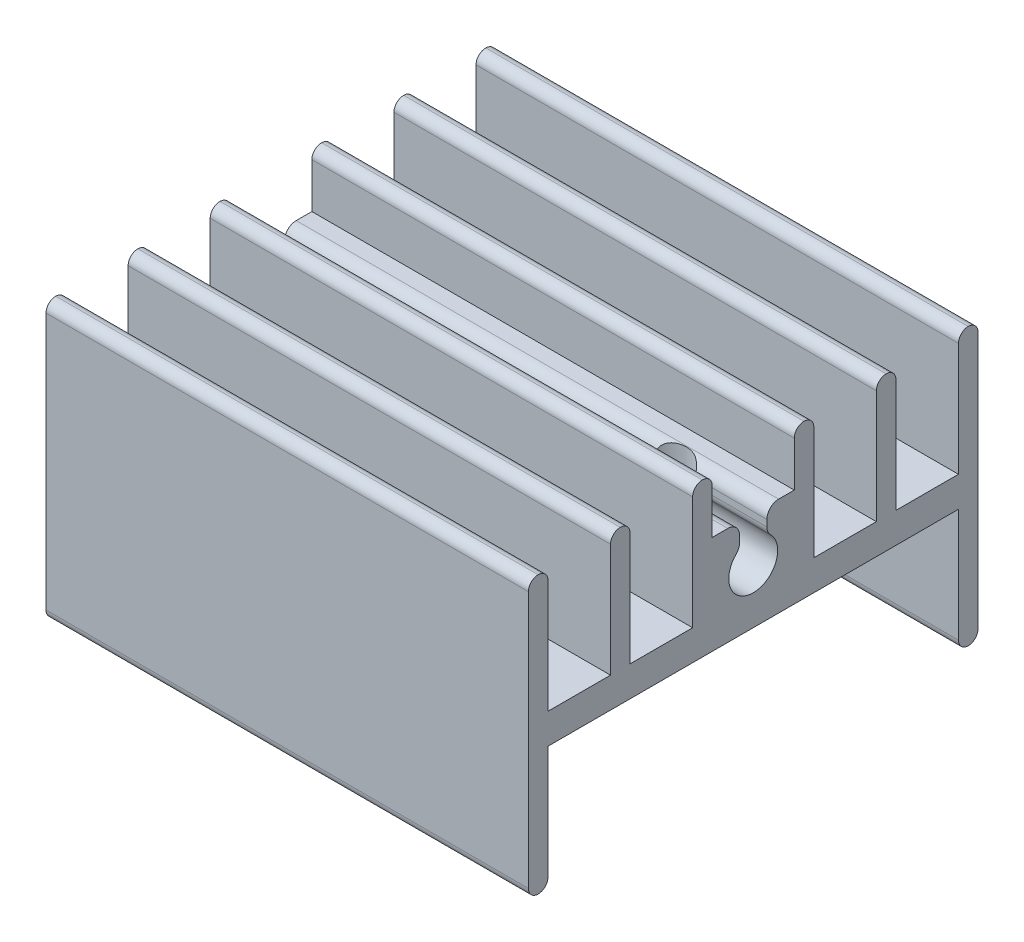
SolidWorks part; units mm, degrees
ref_plane "Front Plane" through (0, 0, 0) normal (0, 0, 1) x (1, 0, 0)
ref_plane "Top Plane" through (0, 0, 0) normal (0, 1, 0) x (1, 0, 0)
ref_plane "Right Plane" through (0, 0, 0) normal (1, 0, 0) x (0, 0, -1)
sketch "Sketch1" plane through (0, 0, 0) normal (0, 1, 0) x (1, 0, 0)
  line L1 (-12.34, 11.5) -> (12.34, 11.5)
  line L2 (-12.34, 11.5) -> (-12.34, -11.5)
  line L3 (-12.34, -11.5) -> (12.34, -11.5)
  line L4 (12.34, 11.5) -> (12.34, -11.5)
  line L5 (-12.34, 11.5) -> (12.34, -11.5) construction
  line L6 (-12.34, -11.5) -> (12.34, 11.5) construction
  point P0 (0, 0)
  dimension "D1" = 24.68
  dimension "D2" = 23
extrude "Boss-Extrude1" add sketch "Sketch1" along normal blind 1.55
sketch "Sketch2" plane through (0, 1.55, 0) normal (0, 1, 0) x (1, 0, 0)
  line L0 (12.34, -11.5) -> (12.34, 11.5) construction
  line L1 (-12.34, 11.5) -> (12.34, 11.5)
  line L2 (-12.34, 11.5) -> (-12.34, 10.5)
  line L3 (-12.34, 10.5) -> (12.34, 10.5)
  line L4 (12.34, 11.5) -> (12.34, 10.5)
  line L6 (-12.34, -11.5) -> (12.34, -11.5)
  line L7 (-12.34, -11.5) -> (-12.34, -10.5)
  line L8 (-12.34, -10.5) -> (12.34, -10.5)
  line L9 (12.34, -11.5) -> (12.34, -10.5)
  dimension "D1" = 1
  dimension "D2" = 1
extrude "Boss-Extrude2" add sketch "Sketch2" along normal blind 6.3 and the other way blind 7.85
sketch "Sketch3" plane through (0, 1.55, 0) normal (0, 1, 0) x (1, 0, 0)
  line L0 (-12.34, 10.5) -> (-12.34, -10.5) construction
  line L1 (-12.34, 7.3) -> (12.34, 7.3)
  line L2 (-12.34, 7.3) -> (-12.34, 6.3)
  line L3 (-12.34, 6.3) -> (12.34, 6.3)
  line L4 (12.34, 7.3) -> (12.34, 6.3)
  line L5 (12.34, -10.5) -> (12.34, 10.5) construction
  line L6 (-12.34, 10.5) -> (12.34, 10.5) construction
  line L8 (-12.34, -6.3) -> (12.34, -6.3)
  line L9 (-12.34, -6.3) -> (-12.34, -7.3)
  line L10 (-12.34, -7.3) -> (12.34, -7.3)
  line L11 (12.34, -6.3) -> (12.34, -7.3)
  dimension "D1" = 3.2
  dimension "D2" = 1
  dimension "D3" = 3.2
  dimension "D4" = 1
extrude "Boss-Extrude3" add sketch "Sketch3" along normal blind 6.3
sketch "Sketch4" plane through (0, 1.55, 0) normal (0, 1, 0) x (1, 0, 0)
  line L0 (-12.34, 6.3) -> (-12.34, -6.3) construction
  line L1 (-12.34, 3.1) -> (12.34, 3.1)
  line L2 (-12.34, 3.1) -> (-12.34, -3.1)
  line L3 (-12.34, -3.1) -> (12.34, -3.1)
  line L4 (12.34, 3.1) -> (12.34, -3.1)
  line L5 (12.34, -6.3) -> (12.34, 6.3) construction
  line L6 (-12.34, 6.3) -> (12.34, 6.3) construction
  line L7 (12.34, -6.3) -> (-12.34, -6.3) construction
  dimension "D1" = 3.2
  dimension "D2" = 3.2
extrude "Boss-Extrude4" add sketch "Sketch4" along normal blind 6.3
sketch "Sketch5" plane through (12.34, 0, 0) normal (1, 0, 0) x (0, 0, -1)
  line L0 (-3.1, 1.55) -> (3.1, 1.55) construction
  line L1 (0, 1.55) -> (0, 7.85) construction
  line L2 (-3.1, 7.85) -> (3.1, 7.85) construction
  line L3 (-2.1, 5.05) -> (-0.7, 5.05)
  line L4 (-3.1, 4.05) -> (-2.1, 4.05) construction
  line L5 (3.1, 7.85) -> (3.1, 1.55) construction
  line L6 (-3.1, 7.85) -> (-3.1, 1.55) construction
  line L7 (-0.7, 5.05) -> (-0.7, 3.8356)
  line L8 (0.7, 5.05) -> (0.7, 3.8356)
  line L9 (0.7, 5.05) -> (2.1, 5.05)
  line L10 (-2.1, 8.15) -> (-2.1, 5.05)
  line L11 (2.1, 8.15) -> (2.1, 5.05)
  line L12 (-2.1, 8.15) -> (2.1, 8.15)
  line L13 (-0.7, 4.05) -> (3.1, 4.05) construction
  arc A0 (-0.7, 3.8356) -> (0.7, 3.8356) centre (0, 2.8) ccw
  point P11 (0, 4.7)
  dimension "D1" = 2.5
  dimension "D2" = 1
  dimension "D3" = 0.7
  dimension "D4" = 1.4
  dimension "D5" = 1
  dimension "D6" = 1
  dimension "D7" = 0.3
extrude "Cut-Extrude1" cut sketch "Sketch5" against normal through all
fillet "Fillet1" radius 0.5 16 edges at (0, -6.3, -11.5) (0, -6.3, -10.5) (0, -6.3, 10.5) (0, -6.3, 11.5) (0, 7.85, -11.5) (0, 7.85, -10.5) (0, 7.85, -7.3) (0, 7.85, -6.3) (0, 7.85, -3.1) (0, 7.85, -2.1) (0, 7.85, 2.1) (0, 7.85, 3.1) (0, 7.85, 6.3) (0, 7.85, 7.3) (0, 7.85, 10.5) (0, 7.85, 11.5)
fillet "Fillet2" radius 0.6 4 edges at (0, 3.8356, -0.7) (0, 5.05, -0.7) (0, 3.8356, 0.7) (0, 5.05, 0.7)
sketch "Sketch6" plane through (0, 0, 0) normal (0, -1, 0) x (1, 0, 0)
  line L0 (12.34, 0) -> (8.92, 0) construction
  line L1 (12.34, 10.5) -> (12.34, -10.5) construction
  circle A0 centre (7.67, 0) radius 1.25
  dimension "D2" = 2.5
  dimension "D1" = 3.42
extrude "Cut-Extrude2" cut sketch "Sketch6" against normal blind 10
